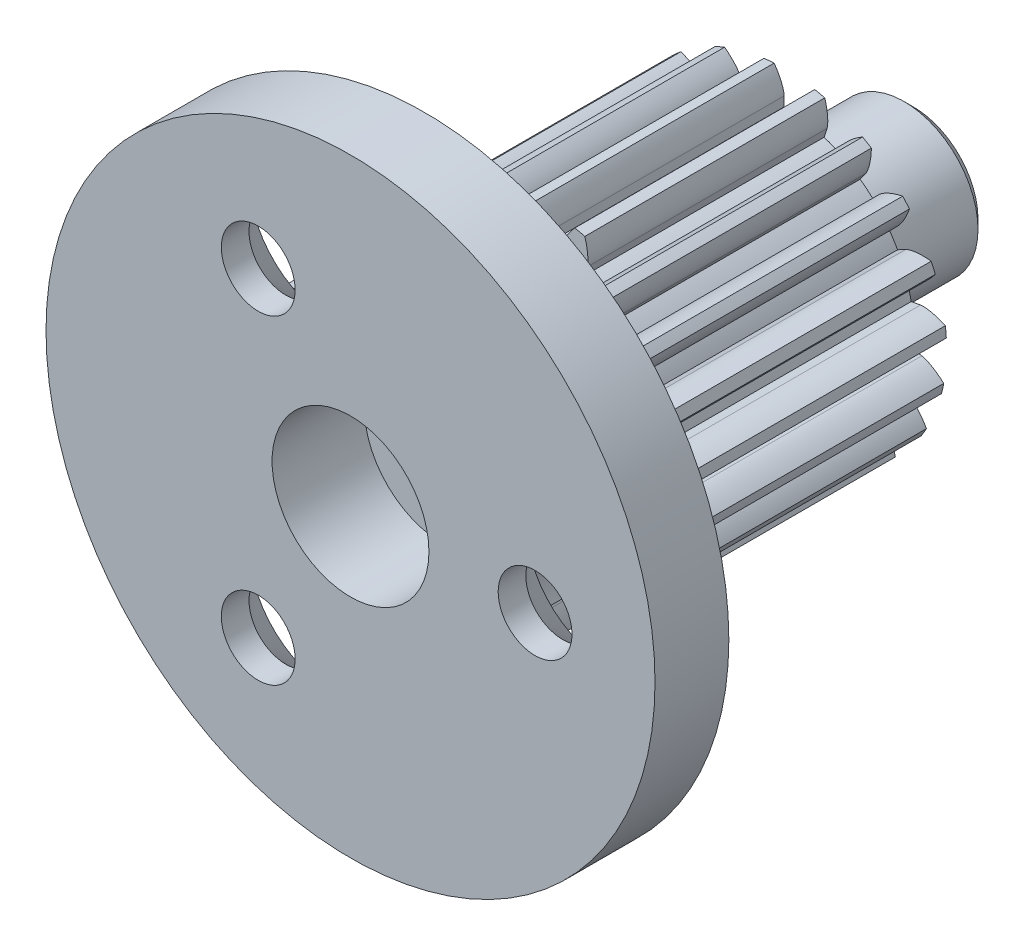
SolidWorks part; units mm, degrees
ref_plane "Front Plane" through (0, 0, 0) normal (0, 0, 1) x (1, 0, 0)
ref_plane "Top Plane" through (0, 0, 0) normal (0, 1, 0) x (1, 0, 0)
ref_plane "Right Plane" through (0, 0, 0) normal (1, 0, 0) x (0, 0, -1)
sketch "Sketch1" plane through (0, 0, 0) normal (0, 0, 1) x (1, 0, 0)
  circle A0 centre (0, 0) radius 8.8
  dimension "D1" = 17.6
extrude "Boss-Extrude1" add sketch "Sketch1" along normal mid plane 19.5
sketch "Sketch2" plane through (0, 0, 0) normal (0, 0, 1) x (1, 0, 0)
  line L0 (0, 0) -> (7.5175, 0) construction
  line L1 (0, 0) -> (7.9838, -0.5087) construction
  line L2 (0, 0) -> (7.4567, -0.9542) construction
  line L3 (7.5175, 0) -> (7, 0)
  line L4 (7.4567, -0.9542) -> (6.9434, -0.8885)
  circle A0 centre (0, 0) radius 8 construction
  circle A1 centre (0, 0) radius 7.5175 construction
  circle A2 centre (0, 0) radius 7
  circle A3 centre (0, 0) radius 8.8 construction
  circle A4 centre (0, 0) radius 8.8
  spline S0 degree 4 poles (7.5175, 0) (7.5201, 0) (7.5273, 0.0003) (7.5496, 0.0017) (7.5933, 0.0065) (7.6472, 0.0155) (7.7088, 0.0287) (7.7679, 0.0436) (7.8183, 0.0577) (7.8683, 0.0731) (7.9179, 0.0896) (7.9778, 0.1109) (8.0492, 0.1383) (8.1321, 0.173) (8.2253, 0.2156) (8.3193, 0.2624) (8.4112, 0.3112) (8.503, 0.3637) (8.5911, 0.4167) (8.6816, 0.4749) (8.7646, 0.5303) (8.8563, 0.5958) (8.93, 0.6497) (9.0257, 0.7244) (9.0818, 0.7697) (9.147, 0.8238) (9.1756, 0.8486) (9.1933, 0.8638) knots 0 0 0 0 0 0.005377 0.015084 0.04661 0.092111 0.119476 0.146842 0.174209 0.201575 0.228941 0.256307 0.307035 0.361767 0.4165 0.471232 0.525964 0.580697 0.635429 0.690161 0.744894 0.799626 0.854358 0.909091 0.954545 1 1 1 1 1 construction
  spline S1 degree 4 poles (7.5175, 0) (7.5201, 0) (7.5273, 0.0003) (7.5496, 0.0017) (7.5933, 0.0065) (7.6472, 0.0155) (7.7088, 0.0287) (7.7679, 0.0436) (7.8183, 0.0577) (7.8683, 0.0731) (7.9179, 0.0896) (7.9778, 0.1109) (8.0492, 0.1383) (8.1321, 0.173) (8.2253, 0.2156) (8.3193, 0.2624) (8.4112, 0.3112) (8.503, 0.3637) (8.5911, 0.4167) (8.6816, 0.4749) (8.7646, 0.5303) (8.8563, 0.5958) (8.93, 0.6497) (9.005, 0.7082) (9.0413, 0.7371) (9.0598, 0.7521) knots 0 0 0 0 0 0.005377 0.015084 0.04661 0.092111 0.119476 0.146842 0.174209 0.201575 0.228941 0.256307 0.307035 0.361767 0.4165 0.471232 0.525964 0.580697 0.635429 0.690161 0.744894 0.799626 0.854358 0.909091 0.909091 0.909091 0.909091 0.909091
  spline S2 degree 4 poles (7.4567, -0.9542) (7.4593, -0.9545) (7.4664, -0.9557) (7.4883, -0.9599) (7.5311, -0.9703) (7.5833, -0.986) (7.6428, -1.0069) (7.6995, -1.0292) (7.7477, -1.0496) (7.7954, -1.0712) (7.8425, -1.0938) (7.8992, -1.1226) (7.9666, -1.1588) (8.0443, -1.2038) (8.1314, -1.2579) (8.2188, -1.3162) (8.3036, -1.3763) (8.388, -1.44) (8.4688, -1.5037) (8.5511, -1.573) (8.6264, -1.6384) (8.7091, -1.7151) (8.7753, -1.7779) (8.8608, -1.8642) (8.9107, -1.9162) (8.9684, -1.9782) (8.9937, -2.0064) (9.0093, -2.0237) knots 0 0 0 0 0 0.005377 0.015084 0.04661 0.092111 0.119476 0.146842 0.174209 0.201575 0.228941 0.256307 0.307035 0.361767 0.4165 0.471232 0.525964 0.580697 0.635429 0.690161 0.744894 0.799626 0.854358 0.909091 0.954545 1 1 1 1 1 construction
  spline S3 degree 4 poles (7.4567, -0.9542) (7.4593, -0.9545) (7.4664, -0.9557) (7.4883, -0.9599) (7.5311, -0.9703) (7.5833, -0.986) (7.6428, -1.0069) (7.6995, -1.0292) (7.7477, -1.0496) (7.7954, -1.0712) (7.8425, -1.0938) (7.8992, -1.1226) (7.9666, -1.1588) (8.0443, -1.2038) (8.1314, -1.2579) (8.2188, -1.3162) (8.3036, -1.3763) (8.388, -1.44) (8.4688, -1.5037) (8.5511, -1.573) (8.6264, -1.6384) (8.7091, -1.7151) (8.7753, -1.7779) (8.8422, -1.8455) (8.8746, -1.8788) (8.891, -1.8959) knots 0 0 0 0 0 0.005377 0.015084 0.04661 0.092111 0.119476 0.146842 0.174209 0.201575 0.228941 0.256307 0.307035 0.361767 0.4165 0.471232 0.525964 0.580697 0.635429 0.690161 0.744894 0.799626 0.854358 0.909091 0.909091 0.909091 0.909091 0.909091
  dimension "D1" = 16
  dimension "D2" = 15.0351
  dimension "D3" = 14
  dimension "D4" = 3.646
  dimension "D5" = 3.646
extrude "Cut-Extrude1" cut sketch "Sketch2" against normal through all both and the other way through all contours A2 S3 A4 S1 region at (8.0236, -0.5113, 0)
pattern_circular "CirPattern2" count 20 over 360 about axis through (0, 0, -9.75) along (0, 0, 1) of "Cut-Extrude1"
sketch "Sketch3" plane through (0, 0, 0) normal (0, 1, 0) x (1, 0, 0)
  line L0 (0, 9.75) -> (0, 20.841) construction
  line L1 (0, 20.841) -> (0, -26.4333) construction
  line L2 (0, 16.75) -> (-4, 16.75)
  line L3 (-4, 16.75) -> (-4, 11.25)
  line L4 (-4, 11.25) -> (-4.5, 11.25)
  line L6 (-4.5, 11.25) -> (-4.5, 9.75)
  line L9 (0, 9.75) -> (-4.5, 9.75)
  line L10 (-0.544, -9.75) -> (0, -9.75) construction
  line L11 (0, -9.75) -> (-16.5, -9.75)
  line L12 (-16.5, -9.75) -> (-16.5, -13.75)
  line L13 (-16.5, -13.75) -> (0, -13.75)
  line L14 (0, 16.75) -> (0, -13.75)
  line L15 (0, 9.75) -> (-0.544, 9.75) construction
  point P7 (0, -9.75)
  point P14 (0, 9.75)
  dimension "D1" = 4
  dimension "D2" = 5.5
  dimension "D3" = 1.5
  dimension "D4" = 0.5
  dimension "D5" = 4
  dimension "D6" = 16.5
revolve "Revolve1" add sketch "Sketch3" angle 360 about L0 region at (-2.0587, 0, -13.1783) region at (-8.25, 0, 11.75)
chamfer "Chamfer1" distance 0.5 angle 45 1 edges at (4.5, 0, -9.75)
chamfer "Chamfer2" distance 0.5 angle 45 1 edges at (4, 0, -16.75)
sketch "Sketch4" plane through (0, 0, 13.75) normal (0, 0, 1) x (1, 0, 0)
  circle A0 centre (0, 0) radius 2.5
  dimension "D1" = 5
extrude "Cut-Extrude2" cut sketch "Sketch4" against normal through all
sketch "Sketch5" plane through (0, 0, 13.75) normal (0, 0, 1) x (1, 0, 0)
  circle A0 centre (0, 0) radius 4.25
  dimension "D1" = 8.5
extrude "Cut-Extrude3" cut sketch "Sketch5" against normal blind 5
sketch "Sketch6" plane through (0, 0, 9.75) normal (0, 0, -1) x (-1, 0, 0)
  line L0 (0, 0) -> (-10, 0) construction
  circle A0 centre (0, 0) radius 10 construction
  circle A1 centre (5, 8.6603) radius 2
  circle A2 centre (5, -8.6603) radius 2
  circle A3 centre (-10, 0) radius 2
  point P14 (0, 0)
  dimension "D1" = 20
  dimension "D2" = 4
  dimension "D3" = 3
extrude "Cut-Extrude4" cut sketch "Sketch6" against normal through all
sketch "Sketch7" plane through (0, 0, 0) normal (0, 1, 0) x (1, 0, 0)
  line L2 (8, -13.75) -> (12, -13.75)
  line L3 (12, -9.75) -> (8, -9.75) construction
  line L4 (10, -9.75) -> (10, -13.75) construction
  line L5 (10, -9.75) -> (14.5, -9.75)
  line L6 (14.5, -9.75) -> (12, -12.25)
  line L7 (12, -12.25) -> (10, -12.25)
  line L8 (10, -9.75) -> (10, -12.25)
  line L9 (12, -9.75) -> (8, -9.75)
  line L10 (8, -13.75) -> (12, -13.75) construction
  line L11 (8, -13.75) -> (12, -13.75)
  dimension "D2" = 4.5
  dimension "D3" = 2
  dimension "D1" = 2.5
revolve "Cut-Revolve1" cut sketch "Sketch7" angle 360 about L4 region at (11.7051, 0, 10.8397)
pattern_circular "CirPattern3" count 3 over 360 about axis through (0, 0, -16.75) along (0, 0, 1) of "Cut-Revolve1"
sketch "Sketch8" plane through (0, 0, 9.75) normal (0, 0, -1) x (-1, 0, 0)
  line L0 (0, 10) -> (0, 0) construction
  circle A0 centre (0, 10) radius 4.5
  circle A1 centre (0, 0) radius 10 construction
  circle A2 centre (8.6603, -5) radius 4.5
  circle A3 centre (-8.6603, -5) radius 4.5
  point P14 (0, 0)
  dimension "D1" = 20
  dimension "D3" = 3
  dimension "D2" = 9
extrude "Cut-Extrude5" cut sketch "Sketch8" along normal blind 6.5
equation "\"Ns\"= 20"
equation "\"module\"= 0.8"
equation "\"pressure angle\"= 20deg"
equation "\"h_a\"= 1 * \"module\"'addendum"
equation "\"h_b\"= 1.25 * \"module\"'dedendum"
equation "\"clr_tip_root\"= \"h_f\" - \"h_a\"'clearance of gear tooth tip and root"
equation "\"dp_s\"= \"module\" * \"Ns\"'PCD"
equation "\"db_s\"= \"dp_s\" * cos ( \"pressure angle\" )'base CD"
equation "\"D1@Sketch1\"=\"dp_s\" + 2*\"h_a\""
equation "\"fw_s_calc\"= 13mm'face width"
equation "\"D1@Boss-Extrude1\"=\"fw_s_used\""
equation "\"D1@Sketch2\"=\"dp_s\""
equation "\"D2@Sketch2\"= \"db_s\""
equation "\"D3@Sketch2\"=\"dp_s\"- 2*\"h_b\""
equation "\"alpha_s\"= sqr ( \"dp_s\" ^ 2 - \"db_s\" ^ 2 ) / \"db_s\" * 180 / pi - \"pressure angle\""
equation "\"D4@Sketch2\"= 360 / ( 4 * \"Ns\" ) - \"alpha_s\""
equation "\"beta_s\"= ( 360 / ( 4 * \"Ns\" ) - \"alpha_s\" ) * 2"
equation "\"D5@Sketch2\"= 360 / ( 4 * \"Ns\" ) - \"alpha_s\""
equation "\"D1@CirPattern2\"=\"Ns\""
equation "\"Np\"= 40"
equation "\"dp_p\"= \"module\" * \"Np\"'PCD"
equation "\"db_p\"= \"dp_p\" * cos ( \"pressure angle\" )'base CD"
equation "\"fw_p\"= \"fw_r\""
equation "\"alpha_p\"= sqr ( \"dp_p\" ^ 2 - \"db_p\" ^ 2 ) / \"db_p\" * 180 / pi - \"pressure angle\""
equation "\"beta_p\"= ( 360 / ( 4 * \"Np\" ) - \"alpha_p\" ) * 2"
equation "\"Nr\"= \"Ns\" + 2 * \"Np\"'num teeth"
equation "\"pressure_angle\"= 20deg"
equation "\"h_f\"= 1.25 * \"module\"'dedendum"
equation "\"dp_r\"= \"module\" * \"Nr\"'PCD"
equation "\"db_r\"= \"dp_r\" * cos ( \"pressure_angle\" )'base CD"
equation "\"fw_r\"= 11.5mm'face width"
equation "\"alpha_r\"= sqr ( \"dp_r\" ^ 2 - \"db_r\" ^ 2 ) / \"db_r\" * 180 / pi - \"pressure_angle\""
equation "\"beta_r\"= ( 360 / ( 4 * \"Nr\" ) + \"alpha_r\" ) * 2"
equation "\"bearing_ID\"= \"module\" * ( \"Ns\" + \"Np\" ) + 10"
equation "\"bearing_OD\"= 1.18 * \"bearing_ID\" + 8.57"
equation "\"bearing_height\"= 0.09 * \"bearing_ID\" + 4.62"
equation "\"clearance_planet\"=1.5"
equation "\"case_dist\"= \"sec_carrier_thickness\" + \"clearance_planet\" + \"sun_coupler_hub_thickness\" + \"standard_clearance_1_5mm\""
equation "\"Motor_case_OD_max\"= \"case_mounting_PCD\" + \"case_mounting_hole_allen_socket_dia\" + \"clearance_case_mount_holes_shell_thickness\" * 2"
equation "\"case_mounting_PCD\"= \"motor_case_OD_base\" + \"case_mounting_hole_shift\" * 2"
equation "\"bearing mount thickness\"= IIF((\"bearing_OD\" + \"output_mounting_hole_dia\" * 4) > (\"Nr\" * \"module\" + 2 * \"h_b\"), \"output_mounting_hole_dia\" * 2, ((\"Nr\" * \"module\" + 2 * \"h_b\" - (\"bearing_OD\" + \"output_mounting_hole_dia\" * 4)) / 2) + \"output_mounting_hole_dia\" * 2 + \"standard_clearance_1_5mm\")"
equation "\"case_mounting_hole_dia\"=3"
equation "\"output_mounting_PCD\"= \"bearing_OD\" + \"bearing mount thickness\""
equation "\"output_mounting_hole_dia\"= 4"
equation "\"clearance_case_mount_holes_shell_thickness\"= 1"
equation "\"motor_case_OD_base\"= \"motor_OD\" + \"clearance_motor_and_case\" * 2 + \"Motor_case_thickness\" * 2"
equation "\"sec_carrier_thickness\"= 5"
equation "\"sun_coupler_hub_thickness\"= 4"
equation "\"clearance_sun_coupler_sec_carrier\"= 1.5"
equation "\"clearance_motor_and_case\"= IIF(\"ring_OD\" < \"motor_OD\", 5, (\"ring_OD\" - \"motor_OD\")/2 + 5)"
equation "\"motor_OD\"= 88.6"
equation "\"Motor_case_thickness\"= 2.5"
equation "\"Motor_case_ID\"= \"motor_OD\" + \"clearance_motor_and_case\" * 2"
equation "\"case_mounting_hole_shift\"= \"case_mounting_hole_dia\" / 2 - 0.5"
equation "\"output_mounting_nut_wrench_size\"= 7"
equation "\"output_mounting_nut_thickness\"= 3.2"
equation "\"case_mounting_hole_allen_socket_dia\"= 5.5"
equation "\"output_mounting_nut_depth\"= 3"
equation "\"case_mounting_bolt_depth\"= 4.5"
equation "\"ring_radial_thickness\"= 5"
equation "\"ring_OD\"= \"Nr\" * \"module\" + \"ring_radial_thickness\" * 2"
equation "\"ring_to_chamfer_clearance\"= 2"
equation "\"Motor_case_OD_base_to_chamfer\"=5"
equation "\"pattern_offset_from_motor_case_OD_base\"= 3"
equation "\"pattern_bulge_dia\"= 3"
equation "\"pattern_num_bulge\"= 18"
equation "\"pattern_depth\"= 2"
equation "\"motor_height\"= 43"
equation "\"case_mounting_wrench_size\"= 5.5"
equation "\"case_mounting_nut_clearance\"= 2"
equation "\"base_plate_thickness\"= 4"
equation "\"case_mounting_nut_thickness\"= 2.4"
equation "\"case_mounting_surface_height\"= 4"
equation "\"motor_mount_hole_PCD\"= 32"
equation "\"motor_mount_hole_dia\"= 4"
equation "\"motor_mount_hole_num\"= 4"
equation "\"central_hole_offset_from_motor_mount_PCD\"= 5"
equation "\"wire_slot_dist_from_center\"= 30"
equation "\"wire_slot_length\"= 10"
equation "\"wire_slot_radius\"= 4"
equation "\"driver_upper_holes_dist_from_center\"= 23"
equation "\"driver_lower_holes_dist_from_center\"= 15"
equation "\"driver_side_holes_dist_from_center\"= 20"
equation "\"driver_mount_holes_dia\"= 2.5"
equation "\"driver_mount_inserts_OD\"= 3.5"
equation "\"driver_mount_thickness\"= 1.5"
equation "\"driver_mount_height\"= 4"
equation "\"air_flow_hole_offset\"= 3"
equation "\"num_planet\"= 3"
equation "\"planet_pin_bolt_dia\"= 5"
equation "\"planet_pin_socket_head_dia\"= 8.5"
equation "\"carrier_PCD\"= ( \"Np\" + \"Ns\" ) * \"module\""
equation "\"planet_shaft_dia\"= 8"
equation "\"planet_shaft_step_offset\"= 1"
equation "\"carrier_trapezoidal_support_sun_offset\"= 5"
equation "\"carrier_trapezoidal_support_hole_PCD_offset_bearing_ID\"= 4"
equation "\"carrier_trapezoidal_support_hole_dia\"= 3"
equation "\"carrier_trapezoidal_support_hole_socket_head_dia\"= 5.5"
equation "\"carrier_bearing_step_width\"= 1.5"
equation "\"standard_clearance_1_5mm\"=1.5"
equation "\"standard_fillet_1_5mm\"= 1.5"
equation "\"sun_shaft_bearing_OD\"= 16"
equation "\"sun_shaft_bearing_width\"= 4"
equation "\"standard_bearing_insertion_chamfer\"= 0.5"
equation "\"carrier_trapezoidal_support_hole_wrench_size\"= 5.5"
equation "\"planet_pin_bolt_wrench_size\"= 8"
equation "\"planet_bearing_OD\"= 12"
equation "\"planet_bearing_width\"= 3"
equation "\"planet_bore\"= 10"
equation "\"stg1_output_hole_PCD\"=20"
equation "\"motor_output_hole_dia\"= 4"
equation "\"motor_output_hole_num\"= 4"
equation "\"sun_shaft_bearing_ID\"= 8"
equation "\"D1@Sketch3\"=\"sun_shaft_bearing_ID\"/2"
equation "\"D2@Sketch3\"=\"sun_shaft_bearing_width\" + \"standard_clearance_1_5mm\""
equation "\"D3@Sketch3\"=\"standard_clearance_1_5mm\""
equation "\"D4@Sketch3\"=\"standard_clearance_1_5mm\"/3"
equation "\"D5@Sketch3\"=\"sun_coupler_hub_thickness\""
equation "\"sun_hub_dia\"= \"motor_output_hole_PCD\" + \"motor_output_hole_dia\" + \"standard_clearance_1_5mm\" * 4"
equation "\"D6@Sketch3\"=\"sun_hub_dia\"/2"
equation "\"D1@Chamfer2\"=\"standard_bearing_insertion_chamfer\""
equation "\"D1@Chamfer1\"=\"standard_bearing_insertion_chamfer\""
equation "\"sun_central_bolt_dia\"= 5"
equation "\"sun_central_bolt_socket_head_dia\"= 8.5"
equation "\"D1@Sketch4\"=\"sun_central_bolt_dia\""
equation "\"D1@Cut-Extrude3\"=\"sun_central_bolt_dia\""
equation "\"D1@Sketch5\"=\"sun_central_bolt_socket_head_dia\""
equation "\"fw_s_used\"= \"fw_p\" + \"clearance_planet\" + \"sec_carrier_thickness\" + \"standard_clearance_1_5mm\""
equation "\"D1@Sketch6\"= \"stg1_carrier_stg2_sun_coupling_pcd\""
equation "\"D2@Sketch6\"= \"stg1_carrier_stg2_sun_coupling_dia\""
equation "\"motor_output_hole_CSK_OD\"= 9'8.96 is exact value"
equation "\"motor_output_hole_CSK_head_height\"= 2.5"
equation "\"D2@Sketch7\"=\"motor_output_hole_CSK_OD\"/2"
equation "\"D3@Sketch7\"=\"stg1_carrier_stg2_sun_coupling_dia\"/2"
equation "\"D1@Sketch7\"=\"motor_output_hole_CSK_head_height\""
equation "\"D1@Sketch8\"=\"stg1_output_hole_PCD\""
equation "\"D2@Sketch8\"=\"motor_output_hole_CSK_OD\""
equation "\"D1@Cut-Extrude5\"=\"sec_carrier_thickness\"+\"standard_clearance_1_5mm\""
equation "\"Cut-Extrude5\"= IIF ( ( \"Ns\" * \"module\" + 2 * \"h_a\" ) < ( \"stg1_output_hole_PCD\" - \"motor_output_hole_CSK_OD\" ) , \"suppressed\" , \"unsuppressed\" )"
equation "\"bearing_retainer_thickness\"= 2"
equation "\"motor_output_hole_PCD\"= 23"
equation "\"Ns1\"= 20"
equation "\"Np1\"= 40"
equation "\"Nr1\"= \"Ns1\" + 2 * \"Np1\"'num teeth"
equation "\"module1\"= 0.8"
equation "\"bearing1_ID\"= \"module1\" * ( \"Ns\" + \"Np\" ) + 10"
equation "\"bearing1_OD\"= 1.18 * \"bearing1_ID\" + 8.57"
equation "\"bearing1_height1\"= 0.09 * \"bearing1_ID\" + 4.62"
equation "\"bearing mount thickness1\"= IIF((\"bearing1_OD\" + \"output_mounting_hole_dia\" * 4) > (\"Nr1\" * \"module1\" + 2 * \"module1\"  * 1.25),\"output_mounting_hole_dia\" * 2, ((\"Nr1\" * \"module1\" + 2 * \"module1\"  * 1.25 - (\"bearing1_OD\" + \"output_mounting_hole_dia\" * 4)) / 2) + \"output_mounting_hole_dia\" * 2 + \"standard_clearance_1_5mm\")"
equation "\"output_mounting_PCD1\"= \"bearing1_OD\" + \"bearing mount thickness1\""
equation "\"num_planet1\"= 3"
equation "\"stg1_stg2_mounting_pattern_width\" = 12"
equation "\"stg1_stg2_allen_socket_head_dia\" = 7"
equation "\"stg1_carrier_stg2_sun_coupling_pcd\" = 20"
equation "\"stg1_carrier_stg2_sun_coupling_dia\" = 4"
equation "\"stg1_carrier_stg2_sun_coupling_nut_wrench\" = 7"
equation "\"stg1_carrier_stg2_sun_coupling_num\" = 3"
equation "\"stg1_carrier_stg2_sun_coupling_nut_thickness\" = 3.2"
equation "\"D3@Sketch6\"=\"stg1_carrier_stg2_sun_coupling_num\""
